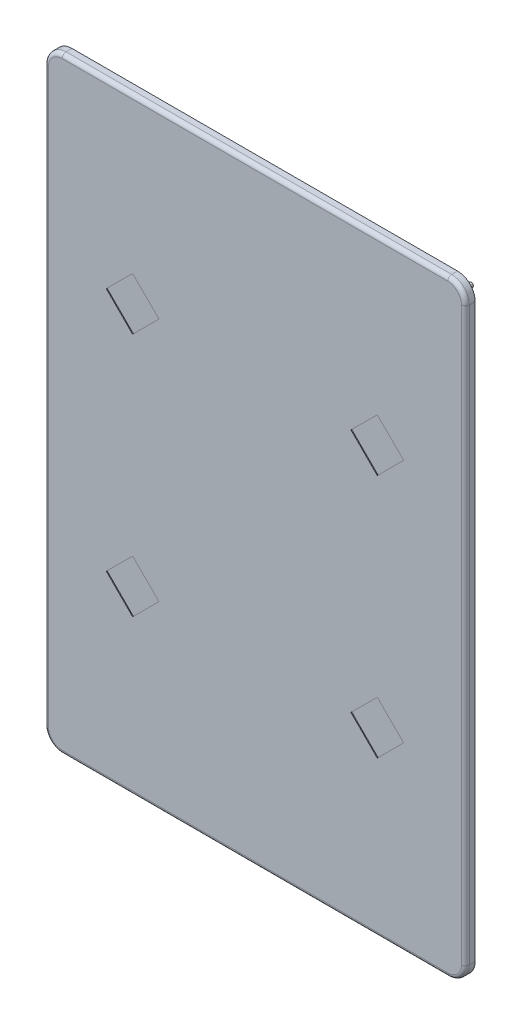
SolidWorks part; units mm, degrees
ref_plane "Front Plane" through (0, 0, 0) normal (0, 0, 1) x (1, 0, 0)
ref_plane "Top Plane" through (0, 0, 0) normal (0, 1, 0) x (1, 0, 0)
ref_plane "Right Plane" through (0, 0, 0) normal (1, 0, 0) x (0, 0, -1)
sketch "Sketch1" plane through (0, 0, 0) normal (0, 0, 1) x (1, 0, 0)
  line L1 (0, 0) -> (273.05, 0)
  line L2 (0, 0) -> (0, 393.7)
  line L3 (0, 393.7) -> (273.05, 393.7)
  line L4 (273.05, 0) -> (273.05, 393.7)
  dimension "D1" = 393.7
  dimension "D2" = 273.05
extrude "Boss-Extrude1" add sketch "Sketch1" along normal blind 6.35
fillet "Fillet2" radius 11.43 4 edges at (0, 0, 3.175) (273.05, 0, 3.175) (0, 393.7, 3.175) (273.05, 393.7, 3.175)
fillet "Fillet1" radius 2.54 8 edges at (136.525, 393.7, 6.35) (273.05, 196.85, 6.35) (136.525, 0, 6.35) (0, 196.85, 6.35) (3.3478, 390.3522, 6.35) (269.7022, 390.3522, 6.35) (269.7022, 3.3478, 6.35) (3.3478, 3.3478, 6.35)
sketch "Sketch2" plane through (0, 0, 0) normal (0, 0, -1) x (-1, 0, 0)
  line L0 (-265.811, 385.826) -> (-7.239, 385.826) construction
  line L1 (-7.239, 385.826) -> (-7.239, 7.874) construction
  line L2 (-7.239, 7.874) -> (-265.811, 7.874) construction
  line L3 (-265.811, 7.874) -> (-265.811, 385.826) construction
  line L4 (-136.525, 393.7) -> (-136.525, 385.826) construction
  line L5 (-261.62, 393.7) -> (-11.43, 393.7) construction
  line L6 (-273.05, 196.85) -> (-265.811, 196.85) construction
  line L7 (-273.05, 11.43) -> (-273.05, 382.27) construction
  circle A0 centre (-265.811, 385.826) radius 1.397
  circle A1 centre (-136.525, 385.826) radius 1.397
  circle A2 centre (-7.239, 385.826) radius 1.397
  circle A3 centre (-136.525, 196.85) radius 1.397 [skipped]
  circle A4 centre (-7.239, 196.85) radius 1.397
  circle A5 centre (-136.525, 7.874) radius 1.397
  circle A6 centre (-7.239, 7.874) radius 1.397
  circle A7 centre (-265.811, 196.85) radius 1.397
  circle A8 centre (-265.811, 7.874) radius 1.397
  dimension "D1" = 2.794
  dimension "D2" = 3
  dimension "D3" = 3
extrude "Boss-Extrude2" add sketch "Sketch2" along normal blind 4.699
ref_plane "Plane1" through (0, 9.779, 0) normal (0, -1, 0) x (-1, 0, 0)
sketch "Sketch3" plane through (0, 9.779, 0) normal (0, -1, 0) x (-1, 0, 0)
  line L0 (-240.03, 0) -> (-240.03, 0.254)
  line L1 (-11.43, 0) -> (-261.62, 0) construction
  line L2 (-240.03, 0.254) -> (-233.7435, 0.254)
  line L3 (-221.869, 0.254) -> (-221.869, 0)
  line L4 (-221.869, 0) -> (-240.03, 0)
  line L5 (-273.05, -3.81) -> (-273.05, 0) construction
  line L6 (-230.9495, 0.254) -> (-230.9495, 1.27) construction
  line L7 (-232.9815, 1.27) -> (-232.9815, 1.016)
  line L8 (-228.9175, 1.27) -> (-228.9175, 1.016)
  line L9 (-228.1555, 0.254) -> (-221.869, 0.254)
  arc A0 (-228.1555, 0.254) -> (-228.9175, 1.016) centre (-228.1555, 1.016) cw
  arc A1 (-228.9175, 1.27) -> (-232.9815, 1.27) centre (-230.9495, 1.27) ccw
  arc A2 (-233.7435, 0.254) -> (-232.9815, 1.016) centre (-233.7435, 1.016) ccw
  point P16 (-228.9175, 0.254)
  dimension "D4" = 0.762
  dimension "D1" = 18.161
  dimension "D2" = 33.02
  dimension "D3" = 0.254
  dimension "D5" = 1.27
extrude "Boss-Extrude3" add sketch "Sketch3" against normal blind 6.35
sketch "Sketch4" plane through (0, 0, 6.35) normal (0, 0, 1) x (1, 0, 0)
  line L0 (198.7917, 276.225) -> (215.9, 293.2416)
  line L1 (40.0417, 276.225) -> (57.15, 293.2416)
  line L2 (40.0417, 276.225) -> (57.15, 259.1167)
  line L3 (57.15, 259.1167) -> (74.2583, 276.225)
  line L4 (57.15, 293.2416) -> (74.2583, 276.225)
  line L5 (198.7917, 276.225) -> (215.9, 259.1167)
  line L6 (215.9, 259.1167) -> (233.0083, 276.225)
  line L7 (215.9, 293.2416) -> (233.0083, 276.225)
  line L8 (198.7917, 117.475) -> (215.9, 134.4916)
  line L9 (198.7917, 117.475) -> (215.9, 100.3667)
  line L10 (215.9, 100.3667) -> (233.0083, 117.475)
  line L11 (215.9, 134.4916) -> (233.0083, 117.475)
  line L12 (40.0417, 117.475) -> (57.15, 134.4916)
  line L13 (40.0417, 117.475) -> (57.15, 100.3667)
  line L14 (57.15, 100.3667) -> (74.2583, 117.475)
  line L15 (57.15, 134.4916) -> (74.2583, 117.475)
  line L16 (74.2583, 276.225) -> (198.7917, 276.225) construction
  line L17 (198.7917, 276.225) -> (198.7917, 117.475) construction
  line L18 (74.2583, 117.475) -> (198.7917, 117.475) construction
  line L19 (74.2583, 117.475) -> (74.2583, 276.225) construction
  line L20 (136.525, 391.16) -> (136.525, 276.225) construction
  line L21 (261.62, 391.16) -> (11.43, 391.16) construction
  line L22 (2.54, 196.85) -> (74.2583, 196.85) construction
  line L23 (2.54, 382.27) -> (2.54, 11.43) construction
  dimension "D1" = 24.13
  dimension "D2" = 24.13
  dimension "D3" = 2
  dimension "D4" = 2
extrude "Cut-Extrude1" cut sketch "Sketch4" against normal blind 0.508
